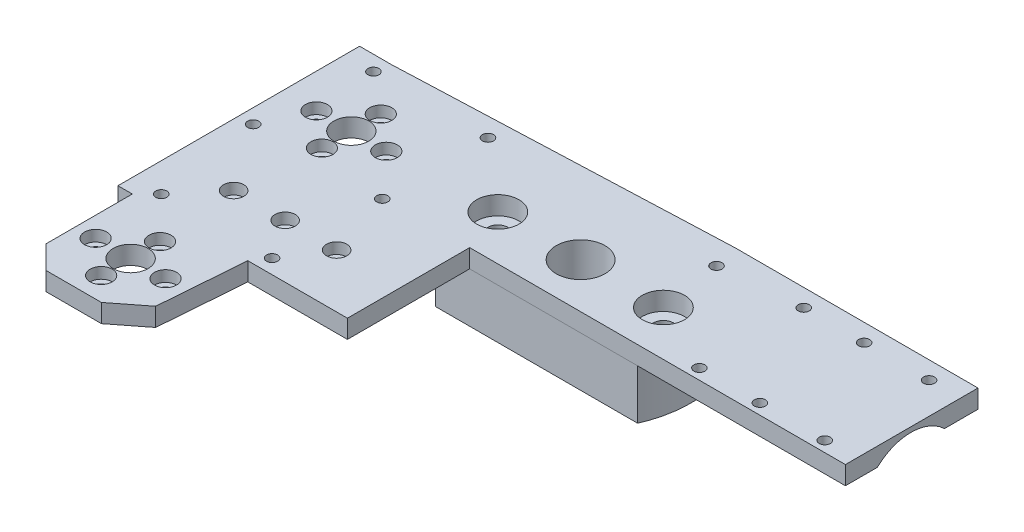
SolidWorks part; units mm, degrees
ref_plane "前视基准面" through (0, 0, 0) normal (0, 0, 1) x (1, 0, 0)
ref_plane "上视基准面" through (0, 0, 0) normal (0, 1, 0) x (1, 0, 0)
ref_plane "右视基准面" through (0, 0, 0) normal (1, 0, 0) x (0, 0, -1)
sketch "Sketch1" plane through (0, 5, 0) normal (0, 1, 0) x (1, 0, 0)
  line L0 (-59.0712, -89.1709) -> (-52.7846, -95.4349)
  line L5 (35.5812, 3.5495) -> (-54.3399, -0.0359)
  line L7 (-54.3399, -0.0359) -> (-62.9727, -0.0359)
  line L8 (-62.9727, 10.8385) -> (-62.9727, -23.8677) construction
  line L9 (-62.9727, -0.0359) -> (-62.9727, -65.7139)
  line L10 (-62.9727, -65.7139) -> (-59.0712, -65.7139)
  line L11 (-59.0712, -65.7139) -> (-59.0712, -89.1709)
  line L12 (-52.7846, -95.4349) -> (-37.7519, -95.4349)
  line L13 (-29.4758, -88.9629) -> (-27.6717, -65.7139)
  line L14 (-27.6717, -65.7139) -> (18.9469, -65.7139)
  line L15 (18.9469, -65.7139) -> (44.4712, -32.6954)
  line L16 (-37.7519, -95.4349) -> (-29.4758, -88.9629)
  line L18 (35.5812, 3.5495) -> (101.5299, 3.5495)
  line L20 (44.4712, -32.6954) -> (101.5299, -32.6954)
  line L21 (101.5299, 3.5495) -> (101.5299, -32.6954)
extrude "Boss-Extrude2" add sketch "Sketch1" against normal blind 5
sketch "Sketch2" plane through (0, 0, 0) normal (0, -1, 0) x (1, 0, 0)
  line L2 (-10.1766, 8.2515) -> (44.8143, 8.2515)
  line L3 (44.8143, 32.2515) -> (-10.1766, 32.2515)
  line L4 (-10.1766, 8.2515) -> (44.8143, 8.2515)
  line L5 (44.8143, 32.2515) -> (-10.1766, 32.2515)
  arc A3 (-10.1766, 32.2515) -> (-10.1766, 8.2515) centre (17.3189, 20.2515) ccw
  arc A4 (44.8143, 8.2515) -> (47.3189, 20.2515) centre (17.3189, 20.2515) ccw
  arc A5 (47.3189, 20.2515) -> (44.8143, 32.2515) centre (17.3189, 20.2515) ccw
  arc A6 (-10.1766, 32.2515) -> (-10.1766, 8.2515) centre (17.3189, 20.2515) ccw
  arc A7 (44.8143, 8.2515) -> (47.3189, 20.2515) centre (17.3189, 20.2515) ccw
  arc A8 (47.3189, 20.2515) -> (44.8143, 32.2515) centre (17.3189, 20.2515) ccw
  dimension "D1" = 0
extrude "Boss-Extrude3" add sketch "Sketch2" along normal up to surface (7.7547 mm away)
chamfer "Chamfer1" distance 5 angle 45 2 edges at (-12.6811, 0, 20.2515) (17.3189, 0, 8.2515)
sketch "Sketch3" plane through (0, 0, 0) normal (0, -1, 0) x (1, 0, 0)
  circle A0 centre (-18.1161, 51.1304) radius 1.25 construction
  circle A1 centre (-32.1161, 51.1304) radius 1.25 construction
  circle A2 centre (-46.1161, 51.1304) radius 1.25 construction
  circle A3 centre (-44.1161, 21.1304) radius 4.75 construction
  circle A4 centre (-44.1161, 81.1304) radius 4.75 construction
  circle A5 centre (-34.6161, 81.1304) radius 1.5 construction
  circle A6 centre (-44.1161, 73.1304) radius 1.5 construction
  circle A7 centre (-53.6161, 81.1304) radius 1.5 construction
  circle A8 centre (-44.1161, 89.1304) radius 1.5 construction
  circle A9 centre (-53.6161, 21.1304) radius 1.5 construction
  circle A10 centre (-44.1161, 13.1304) radius 1.5 construction
  circle A11 centre (-34.6161, 21.1304) radius 1.5 construction
  circle A12 centre (-44.1161, 29.1304) radius 1.5 construction
  circle A13 centre (-18.1161, 51.1304) radius 1.25
  circle A14 centre (-32.1161, 51.1304) radius 1.25
  circle A15 centre (-46.1161, 51.1304) radius 1.25
  circle A16 centre (-44.1161, 21.1304) radius 4.75
  circle A17 centre (-44.1161, 81.1304) radius 4.75
  circle A18 centre (-34.6161, 81.1304) radius 1.5
  circle A19 centre (-44.1161, 73.1304) radius 1.5
  circle A20 centre (-53.6161, 81.1304) radius 1.5
  circle A21 centre (-44.1161, 89.1304) radius 1.5
  circle A22 centre (-53.6161, 21.1304) radius 1.5
  circle A23 centre (-44.1161, 13.1304) radius 1.5
  circle A24 centre (-34.6161, 21.1304) radius 1.5
  circle A25 centre (-44.1161, 29.1304) radius 1.5
extrude "Cut-Extrude1" cut sketch "Sketch3" against normal up to next
sketch "Sketch4" plane through (0, -7.7547, 0) normal (0, -1, 0) x (1, 0, 0)
  arc A0 (-2.4311, 20.2515) -> (-7.9311, 20.2515) centre (-5.1811, 20.2515) ccw construction
  arc A1 (-2.4311, 20.2515) -> (-7.9311, 20.2515) centre (-5.1811, 20.2515) ccw
  arc A2 (-7.9311, 20.2515) -> (-2.4311, 20.2515) centre (-5.1811, 20.2515) ccw construction
  arc A3 (-7.9311, 20.2515) -> (-2.4311, 20.2515) centre (-5.1811, 20.2515) ccw
  arc A4 (37.0689, 20.2515) -> (42.5689, 20.2515) centre (39.8189, 20.2515) ccw construction
  arc A5 (42.5689, 20.2515) -> (37.0689, 20.2515) centre (39.8189, 20.2515) ccw construction
  arc A6 (37.0689, 20.2515) -> (42.5689, 20.2515) centre (39.8189, 20.2515) ccw
  arc A7 (42.5689, 20.2515) -> (37.0689, 20.2515) centre (39.8189, 20.2515) ccw
  circle A8 centre (17.3189, 20.2515) radius 6.6317
extrude "Cut-Extrude2" cut sketch "Sketch4" against normal up to next
sketch "Sketch5" plane through (0, 0, 0) normal (0, -1, 0) x (-1, 0, 0)
  line L0 (-42.0373, -3.2515) -> (13.2753, -3.2515) construction
  circle A0 centre (55.0999, -4.1405) radius 1.5
  circle A1 centre (59.0584, -32.8749) radius 1.5
  circle A2 centre (23.9736, -4.1405) radius 1.5
  circle A3 centre (23.9736, -32.8749) radius 1.5
  circle A4 centre (-37.259, -36.7962) radius 1.5
  circle A5 centre (-14.4681, -36.7962) radius 1.5
  circle A6 centre (18.1161, -51.1304) radius 1.25 construction
  circle A7 centre (32.1161, -51.1304) radius 1.25 construction
  circle A8 centre (46.1161, -51.1304) radius 1.25 construction
  circle A9 centre (18.1161, -51.1304) radius 1.25
  circle A10 centre (32.1161, -51.1304) radius 1.25
  circle A11 centre (46.1161, -51.1304) radius 1.25
  circle A12 centre (55.0999, -61.8073) radius 1.5
  circle A13 centre (24.9827, -61.8073) radius 1.5
  circle A14 centre (-16.8841, -61.8073) radius 1.5
  circle A15 centre (-37.259, -3.2515) radius 1.5
  dimension "D1" = 3
extrude "Cut-Extrude3" cut sketch "Sketch5" against normal up to next (5 mm away)
sketch "Sketch6" plane through (0, 0, 0) normal (0, -1, 0) x (1, 0, 0)
  circle A1 centre (37.259, 3.2515) radius 3.4917
extrude "Cut-Extrude4" cut sketch "Sketch6" along normal blind 16
sketch "Sketch7" plane through (0, 5, 0) normal (0, 1, 0) x (1, 0, 0)
  circle A7 centre (-44.1161, -89.1304) radius 3
  circle A8 centre (-44.1161, -89.1304) radius 3
  circle A10 centre (-34.6161, -81.1304) radius 3
  circle A11 centre (-34.6161, -81.1304) radius 3
  circle A13 centre (-53.6161, -81.1304) radius 3
  circle A14 centre (-53.6161, -81.1304) radius 3
  circle A16 centre (-44.1161, -73.1304) radius 3
  circle A17 centre (-44.1161, -73.1304) radius 3
  circle A19 centre (-44.1161, -29.1304) radius 3
  circle A20 centre (-44.1161, -29.1304) radius 3
  circle A22 centre (-34.6161, -21.1304) radius 3
  circle A23 centre (-34.6161, -21.1304) radius 3
  circle A25 centre (-53.6161, -21.1304) radius 3
  circle A26 centre (-53.6161, -21.1304) radius 3
  circle A28 centre (-44.1161, -13.1304) radius 3
  circle A29 centre (-44.1161, -13.1304) radius 3
  circle A31 centre (-18.1161, -51.1304) radius 2.75
  circle A32 centre (-18.1161, -51.1304) radius 2.75
  circle A34 centre (-32.1161, -51.1304) radius 2.75
  circle A35 centre (-32.1161, -51.1304) radius 2.75
  circle A37 centre (-46.1161, -51.1304) radius 2.75
  circle A38 centre (-46.1161, -51.1304) radius 2.75
  circle A44 centre (39.8189, -20.2515) radius 5.75
  circle A45 centre (39.8189, -20.2515) radius 5.75
  circle A47 centre (-5.1811, -20.2515) radius 5.75
  circle A48 centre (-5.1811, -20.2515) radius 5.75
  dimension "D1" = 1.5
  dimension "D2" = 1.5
  dimension "D3" = 1.5
  dimension "D4" = 1.5
  dimension "D5" = 1.5
  dimension "D6" = 1.5
  dimension "D7" = 1.5
  dimension "D8" = 1.5
  dimension "D9" = 1.5
  dimension "D10" = 1.5
  dimension "D11" = 1.5
  dimension "D12" = 3
  dimension "D13" = 3
extrude "Cut-Extrude5" cut sketch "Sketch7" against normal blind 3
sketch "Sketch8" plane through (0, 2, 0) normal (0, 1, 0) x (1, 0, 0)
  circle A0 centre (-5.1811, -20.2515) radius 5.75 construction
  circle A1 centre (39.8189, -20.2515) radius 5.75 construction
  circle A2 centre (-5.1811, -20.2515) radius 5.75
  circle A3 centre (39.8189, -20.2515) radius 5.75
  circle A4 centre (39.8189, -20.2515) radius 2.75 construction
  circle A5 centre (-5.1811, -20.2515) radius 2.75 construction
  circle A6 centre (-5.1811, -20.2515) radius 2.75
  circle A7 centre (39.8189, -20.2515) radius 2.75
extrude "Cut-Extrude6" cut sketch "Sketch8" against normal blind 2
sketch "Sketch9" plane through (0, -7.7547, 0) normal (0, -1, 0) x (1, 0, 0)
  line L2 (-10.1766, 8.2515) -> (44.8143, 8.2515)
  line L3 (44.8143, 32.2515) -> (-10.1766, 32.2515)
  line L4 (-10.1766, 8.2515) -> (44.8143, 8.2515)
  line L5 (44.8143, 32.2515) -> (-10.1766, 32.2515)
  circle A0 centre (-5.1811, 20.2515) radius 2.75 construction
  circle A1 centre (39.8189, 20.2515) radius 2.75 construction
  arc A2 (44.8143, 8.2515) -> (44.8143, 32.2515) centre (17.3189, 20.2515) ccw
  arc A3 (-10.1766, 32.2515) -> (-10.1766, 8.2515) centre (17.3189, 20.2515) ccw
  arc A4 (44.8143, 8.2515) -> (44.8143, 32.2515) centre (17.3189, 20.2515) ccw
  arc A5 (-10.1766, 32.2515) -> (-10.1766, 8.2515) centre (17.3189, 20.2515) ccw
  circle A6 centre (17.3189, 20.2515) radius 6.6317 construction
  circle A7 centre (-5.1811, 20.2515) radius 2.75
  circle A8 centre (39.8189, 20.2515) radius 2.75
  circle A9 centre (17.3189, 20.2515) radius 6.6317
  dimension "D1" = 0
extrude "Boss-Extrude4" add sketch "Sketch9" along normal blind 6
sketch "草图2" plane through (0, 5, 0) normal (0, 1, 0) x (1, 0, 0)
  line L8 (-0.6026, -32.4866) -> (-0.6026, -71.2304)
  line L9 (-0.6026, -71.2304) -> (116.7944, -71.2304)
  line L10 (116.7944, -71.2304) -> (116.7944, -32.4866)
  line L11 (116.7944, -32.4866) -> (-0.6026, -32.4866)
extrude "切除-拉伸1" cut sketch "草图2" against normal blind 10
sketch "草图3" plane through (52.2273, 0, 0) normal (-1, 0, 0) x (0, 0, 1)
  circle A5 centre (14.68, -9.5341) radius 13.2
extrude "切除-拉伸2" cut sketch "草图3" against normal blind 67 and the other way blind 4
sketch "草图4" plane through (0, 0, 0) normal (0, -1, 0) x (1, 0, 0)
  circle A0 centre (75.3855, 1.2487) radius 1.5
  circle A1 centre (58.9612, 1.2487) radius 1.5
  circle A2 centre (93.0274, 1.2487) radius 1.5
  circle A3 centre (93.0274, 29.5972) radius 1.5
  circle A4 centre (75.3855, 29.5972) radius 1.5
  circle A5 centre (58.9612, 29.5972) radius 1.5
  point P12 (75.3855, 1.2487)
  point P13 (0, 0)
  point P14 (58.9612, 1.2487)
  point P15 (93.0274, 1.2487)
extrude "切除-拉伸3" cut sketch "草图4" against normal through all
